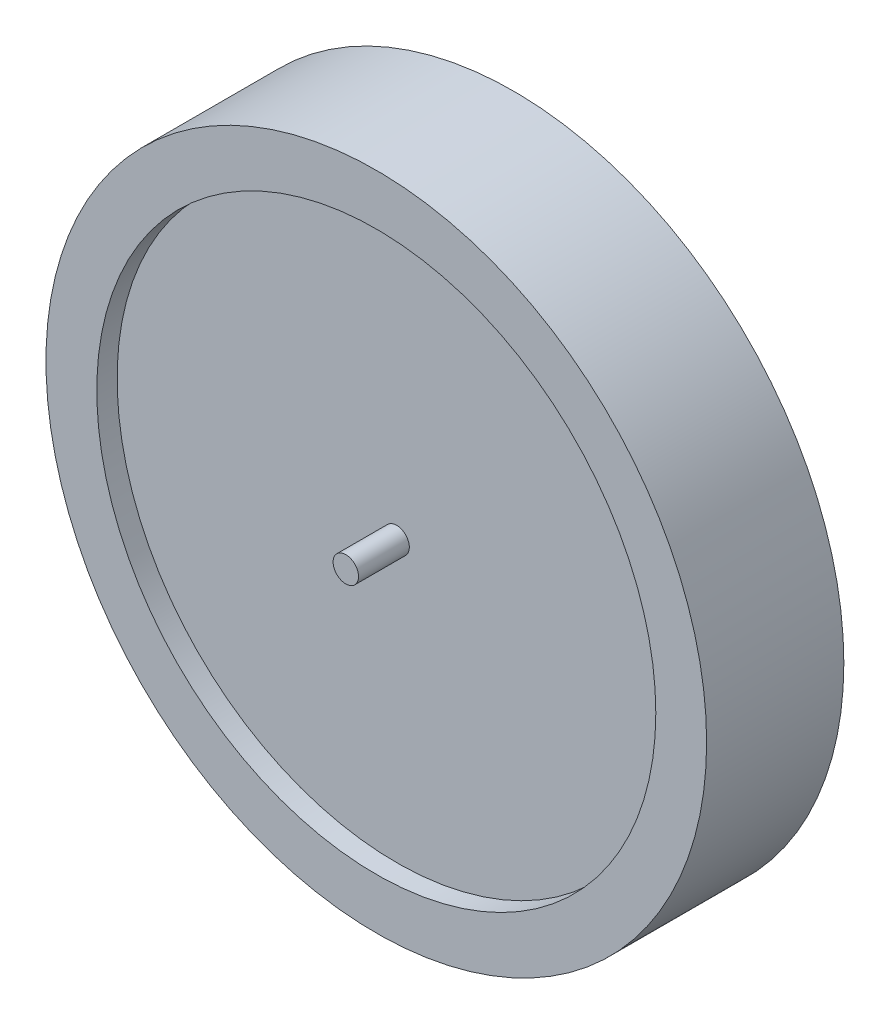
SolidWorks part; units mm, degrees
ref_plane "Front Plane" through (0, 0, 0) normal (0, 0, 1) x (1, 0, 0)
ref_plane "Top Plane" through (0, 0, 0) normal (0, 1, 0) x (1, 0, 0)
ref_plane "Right Plane" through (0, 0, 0) normal (1, 0, 0) x (0, 0, -1)
sketch "Sketch1" plane through (0, 0, 0) normal (0, 0, 1) x (1, 0, 0)
  circle A0 centre (0, 0) radius 65
extrude "Boss-Extrude1" add sketch "Sketch1" along normal blind 27
sketch "Sketch3" plane through (0, 0, 27) normal (0, 0, 1) x (1, 0, 0)
  circle A2 centre (0, 0) radius 55
  circle A3 centre (0, 0) radius 55
  dimension "D1" = 10
extrude "Cut-Extrude1" cut sketch "Sketch3" against normal blind 4
sketch "Sketch4" plane through (0, 0, 0) normal (0, 0, -1) x (-1, 0, 0)
  circle A2 centre (0, 0) radius 55
  circle A3 centre (0, 0) radius 55
  dimension "D1" = 10
extrude "Cut-Extrude2" cut sketch "Sketch4" against normal blind 4
sketch "Sketch5" plane through (0, 0, 23) normal (0, 0, 1) x (1, 0, 0)
  circle A0 centre (0, 0) radius 2.5
  dimension "D1" = 5
extrude "Boss-Extrude2" add sketch "Sketch5" along normal blind 10 and the other way blind 30
